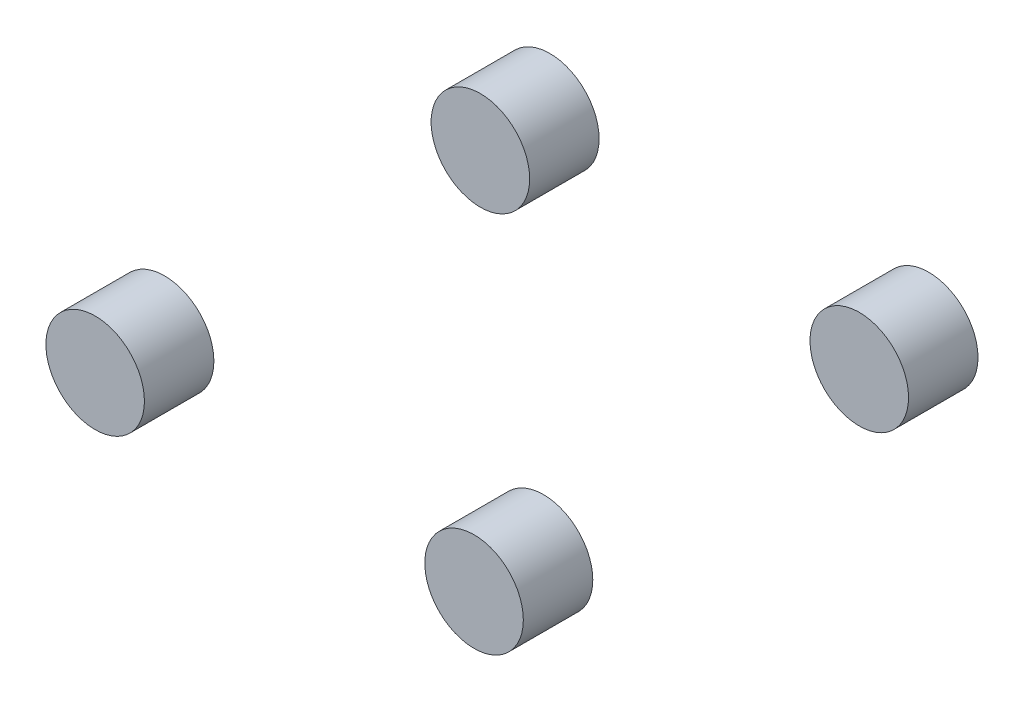
SolidWorks part; units mm, degrees
ref_plane "Front" through (0, 0, 0) normal (0, 0, 1) x (1, 0, 0)
ref_plane "Top" through (0, 0, 0) normal (0, 1, 0) x (1, 0, 0)
ref_plane "Right" through (0, 0, 0) normal (1, 0, 0) x (0, 0, -1)
sketch "Sketch1" plane through (0, 0, 0) normal (0, 0, 1) x (1, 0, 0)
  line L0 (55, 0) -> (-55, 0) construction
  line L1 (-190.5, 0) -> (190.5, 0) construction
  circle A0 centre (-190.5, 0) radius 49.53
  circle A1 centre (190.5, 0) radius 49.53
  point P7 (0, 0)
  point P8 (0, 0)
  point P9 (0, 0)
  dimension "D1" = 99.06
  dimension "D2" = 381
extrude "Boss-Extrude1" add sketch "Sketch1" against normal blind 69.85 from offset 228.6
mirror "Mirror3" about plane through (0, 0, 0) normal (0, 0, 1) of bodies 101 102
